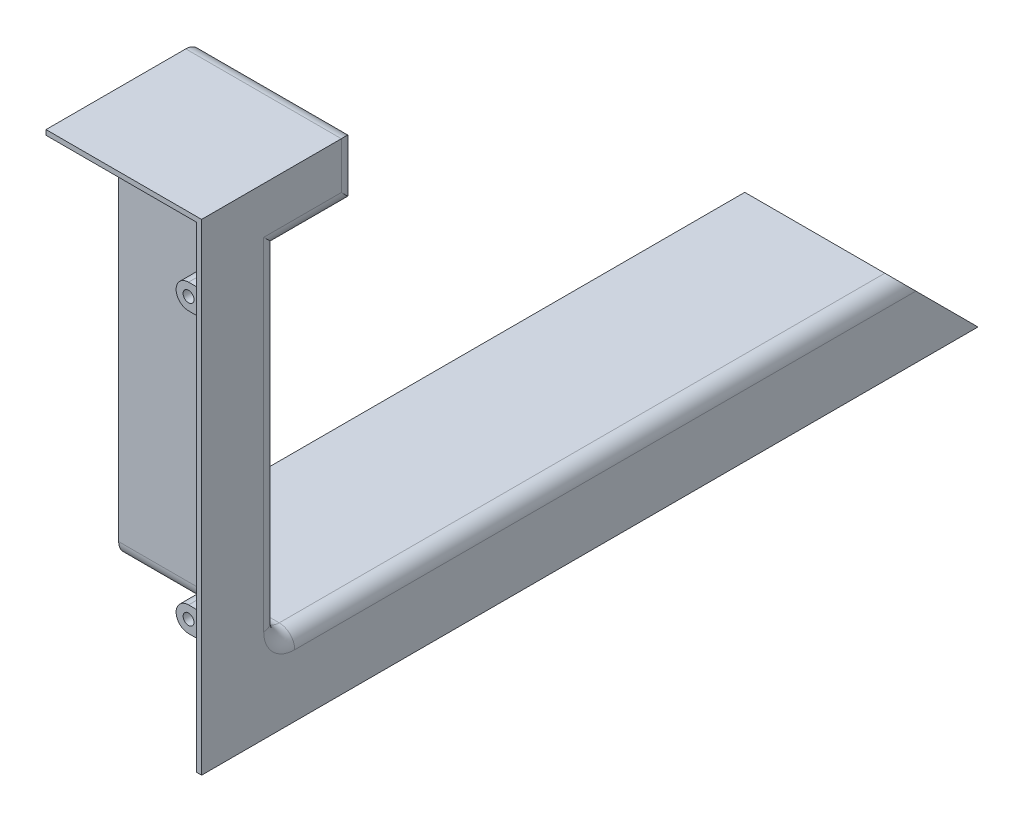
SolidWorks part; units mm, degrees
ref_plane "Front Plane" through (0, 0, 0) normal (0, 0, 1) x (1, 0, 0)
ref_plane "Top Plane" through (0, 0, 0) normal (0, 1, 0) x (1, 0, 0)
ref_plane "Right Plane" through (0, 0, 0) normal (1, 0, 0) x (0, 0, -1)
sketch "Sketch1" plane through (0, 0, 0) normal (1, 0, 0) x (0, 0, -1)
  line L0 (0, 155) -> (0, 0)
  line L1 (0, 0) -> (250, 0)
  line L2 (250, 0) -> (225, 25)
  line L3 (225, 25) -> (25, 25)
  line L4 (25, 25) -> (25, 135)
  line L5 (25, 155) -> (0, 155)
  line L6 (25, 155) -> (50, 155)
  line L7 (50, 155) -> (50, 135)
  line L8 (50, 135) -> (25, 135)
  dimension "D1" = 155
  dimension "D2" = 250
  dimension "D3" = 25
  dimension "D4" = 25
  dimension "D5" = 45
  dimension "D6" = 25
  dimension "D7" = 20
  dimension "D8" = 25
extrude "Boss-Extrude1" add sketch "Sketch1" along normal blind 1.6
sketch "Sketch2" plane through (0, 0, 0) normal (1, 0, 0) x (0, 0, -1)
  line L0 (225, 25) -> (25, 25) construction
  line L1 (25, 25) -> (25, 135) construction
  line L2 (25, 135) -> (50, 135) construction
  line L3 (50, 135) -> (50, 155) construction
  line L4 (50, 155) -> (0, 155) construction
  line L5 (225, 25) -> (25, 25)
  line L6 (25, 25) -> (25, 135)
  line L7 (25, 135) -> (50, 135)
  line L8 (50, 135) -> (50, 155)
  line L9 (50, 155) -> (0, 155)
  line L10 (225, 25) -> (225, 1.6)
  line L11 (223.4, 0) -> (250, 0)
  line L12 (48.4, 153.4) -> (0, 153.4)
  line L13 (48.4, 136.6) -> (48.4, 153.4)
  line L14 (23.4, 136.6) -> (48.4, 136.6)
  line L15 (23.4, 23.4) -> (23.4, 136.6)
  line L16 (223.4, 23.4) -> (23.4, 23.4)
  line L17 (223.4, 23.4) -> (223.4, 0)
  line L18 (0, 155) -> (0, 153.4)
  line L21 (225, 1.6) -> (248.4, 1.6)
  line L22 (250, 0) -> (225, 25) construction
  line L23 (248.4, 1.6) -> (250, 0)
  line L25 (225, 25) -> (225, 0) construction
  dimension "D2" = 1.6
  dimension "D1" = 1.6
extrude "Boss-Extrude2" add sketch "Sketch2" against normal blind 48.5
fillet "Fillet1" radius 5 12 edges at (1.6, 80, -25) (0, 80, -23.4) (1.6, 145, -50) (1.6, 135, -37.5) (0, 145, -48.4) (0, 136.6, -35.9) (-23.45, 155, -50) (-24.25, 153.4, -48.4) (-24.25, 23.4, -23.4) (-23.45, 25, -25) (1.6, 25, -125) (0, 23.4, -123.4)
fillet "Fillet2" radius 5 2 edges at (0, 12.633, -225) (0, 1.6, -236.7)
ref_plane "Plane1" through (0, 6, 0) normal (0, -1, 0) x (-1, 0, 0)
sketch "Sketch3" plane through (0, 6, 0) normal (0, -1, 0) x (1, 0, 0)
  line L0 (-48.5, -223.4) -> (-48.5, -144.7093) construction
  line L1 (0, -34.5) -> (-1.6381, -34.5)
  line L2 (-1.6381, -32.0028) -> (0, -31.5)
  line L3 (-1.6381, -211.5) -> (0, -211.5)
  line L4 (0, -214.5) -> (-1.6381, -214.9988)
  line L5 (0, -31.5) -> (0, -34.5)
  line L6 (0, -211.5) -> (0, -214.5)
  line L13 (-98.6, 0) -> (-98.6, -250)
  line L14 (-98.6, -250) -> (-48.5, -250)
  line L15 (-48.5, -250) -> (-48.5, -223.4)
  line L16 (-48.5, -223.4) -> (-97, -223.4)
  line L17 (-97, -223.4) -> (-97, 0)
  line L18 (-90, -33.4) -> (-7.114, -33.4) construction
  line L19 (-7.114, -213.4) -> (-90, -213.4) construction
  line L20 (0, -28.4) -> (0, -223.4) construction
  line L24 (-97, 0) -> (-98.6, 0)
  line L25 (-98.6, 0) -> (-98.6, -250) construction
  line L26 (-98.6, -250) -> (-48.5, -250) construction
  line L27 (-48.5, -250) -> (-48.5, -223.4) construction
  line L28 (-48.5, -223.4) -> (-97, -223.4) construction
  line L29 (-97, -223.4) -> (-97, 0) construction
  line L36 (-97, 0) -> (-98.6, 0) construction
  arc A0 (-3.9375, -35.5731) -> (-1.6381, -34.5) centre (-1.6381, -37.5) cw
  arc A1 (-3.9375, -35.5731) -> (-4.3217, -30.7513) centre (-7.114, -33.4) cw
  arc A2 (-1.6381, -32.0028) -> (-4.3217, -30.7513) centre (-1.6381, -28.5) cw
  arc A3 (-1.6381, -211.5) -> (-3.9361, -210.4286) centre (-1.6381, -208.5) cw
  arc A4 (-3.5218, -215.8545) -> (-3.9361, -210.4286) centre (-7.114, -213.4) cw
  arc A5 (-3.5218, -215.8545) -> (-1.6381, -214.9988) centre (-1.6381, -217.5) cw
  circle A18 centre (-7.114, -213.4) radius 1.5
  circle A19 centre (-90, -213.4) radius 1.5 construction
  circle A20 centre (-7.114, -33.4) radius 1.5
  circle A21 centre (-90, -33.4) radius 1.5 construction
  point P13 (0, 0)
  dimension "D1" = 0
extrude "Boss-Extrude3" add sketch "Sketch3" against normal up to next contours L2 A2 A1 A0 L1 A20 | A4 A5 L4 L3 A3 A18 region at (-0.819, 6, -34.366) region at (-0.819, 6, -211.6439)
ref_plane "Plane2" through (0, 0, -3.9) normal (0, 0, 1) x (1, 0, 0)
sketch "Sketch4" plane through (0, 0, -3.9) normal (0, 0, 1) x (1, 0, 0)
  line L1 (-6.5, 131.5) -> (0, 131.5)
  line L3 (-6.5, 123.5) -> (0, 123.5)
  line L4 (0, 131.5) -> (0, 123.5)
  line L5 (-6.5, 41.5) -> (0, 41.5)
  line L7 (-6.5, 33.5) -> (0, 33.5)
  line L8 (0, 41.5) -> (0, 33.5)
  circle A0 centre (-6.5, 127.5) radius 1.75 construction
  circle A1 centre (-6.5, 37.5) radius 1.75 construction
  circle A2 centre (-6.5, 127.5) radius 1.75
  circle A3 centre (-6.5, 37.5) radius 1.75
  arc A4 (-6.5, 131.5) -> (-6.5, 123.5) centre (-6.5, 127.5) ccw
  arc A5 (-6.5, 41.5) -> (-6.5, 33.5) centre (-6.5, 37.5) ccw
  dimension "D1" = 8
extrude "Boss-Extrude4" add sketch "Sketch4" against normal up to surface (19.5 mm away) up to face at (-26.75, 82.5, -23.4)
equation "\"D2@Sketch2\"=\"D1@Sketch2\""
